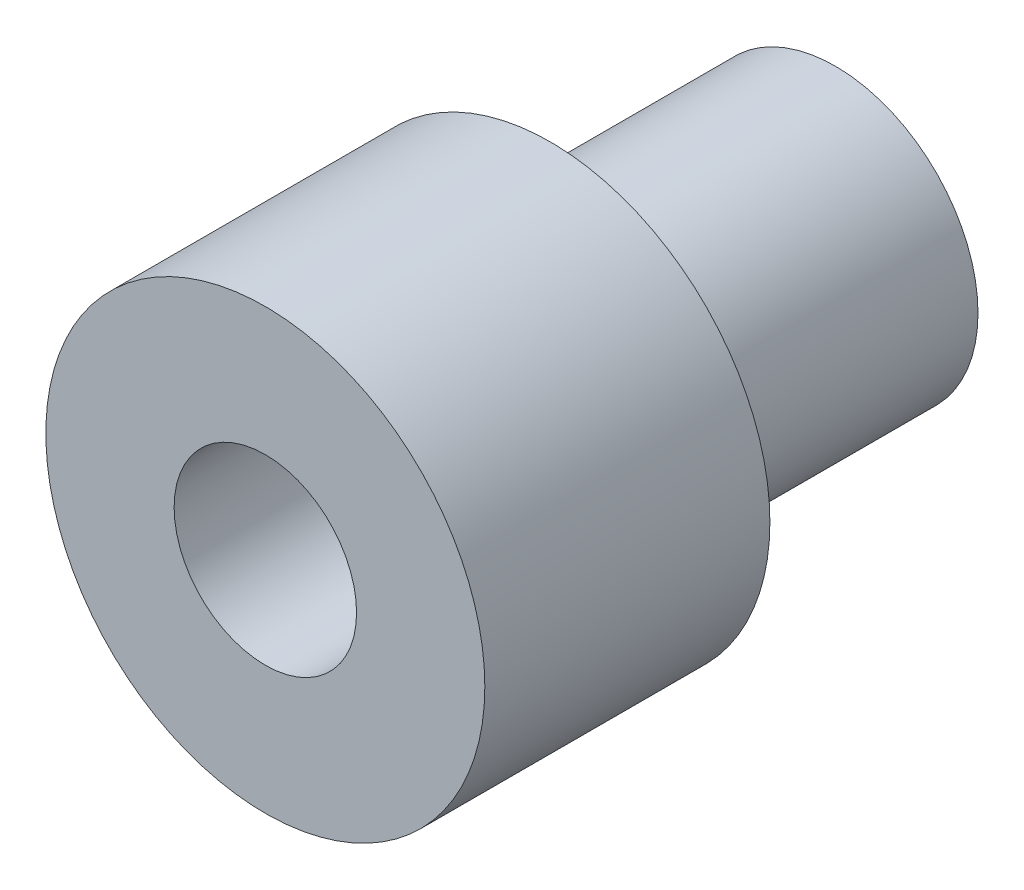
SolidWorks part; units mm, degrees
ref_plane "Front Plane" through (0, 0, 0) normal (0, 0, 1) x (1, 0, 0)
ref_plane "Top Plane" through (0, 0, 0) normal (0, 1, 0) x (1, 0, 0)
ref_plane "Right Plane" through (0, 0, 0) normal (1, 0, 0) x (0, 0, -1)
sketch "Sketch1" plane through (0, 0, 0) normal (1, 0, 0) x (0, 0, -1)
  line L0 (0, 1.6) -> (0, 3.85)
  line L1 (0, 3.85) -> (5, 3.85)
  line L2 (5, 3.85) -> (5, 2.5)
  line L3 (5, 2.5) -> (10, 2.5)
  line L4 (10, 2.5) -> (10, 1.6)
  line L5 (0, 1.6) -> (10, 1.6)
  line L6 (0, 0) -> (10, 0) construction
  point P9 (8, 0)
  point P11 (0, 0)
  dimension "D1" = 3.2
  dimension "D2" = 5
  dimension "D3" = 7.7
  dimension "D4" = 5
  dimension "D5" = 5
revolve "Revolve1" add sketch "Sketch1" angle 360 about L6
